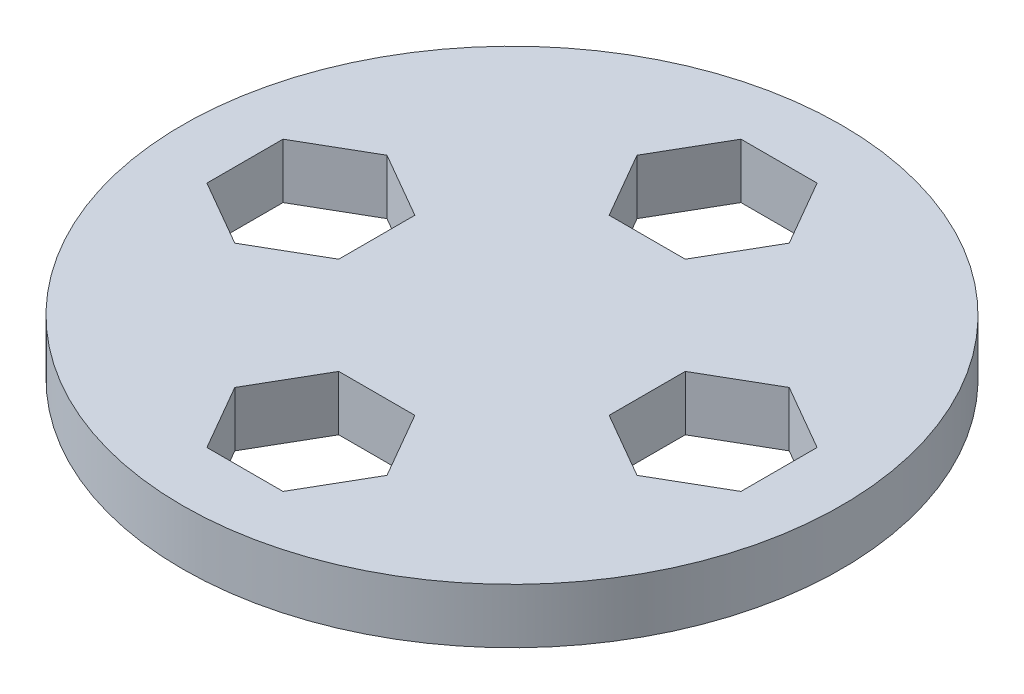
SolidWorks part; units mm, degrees
ref_plane "Alzado" through (0, 0, 0) normal (0, 0, 1) x (1, 0, 0)
ref_plane "Planta" through (0, 0, 0) normal (0, 1, 0) x (1, 0, 0)
ref_plane "Vista lateral" through (0, 0, 0) normal (1, 0, 0) x (0, 0, -1)
sketch "Croquis1" plane through (0, 0, 0) normal (0, 1, 0) x (1, 0, 0)
  circle A0 centre (0, 0) radius 8.5
  dimension "D1" = 17
extrude "Saliente-Extruir1" add sketch "Croquis1" along normal blind 2
sketch "Croquis2" plane through (0, 2, 0) normal (0, 1, 0) x (1, 0, 0)
  circle A0 centre (0, 0) radius 7.5
  dimension "D1" = 15
extrude "Saliente-Extruir2" add sketch "Croquis2" along normal blind 4
sketch "Croquis3" plane through (0, 6, 0) normal (0, 1, 0) x (1, 0, 0)
  circle A0 centre (0, 0) radius 15
  dimension "D1" = 30
extrude "Saliente-Extruir3" add sketch "Croquis3" along normal blind 2.5
fillet "Redondeo1" radius 3 1 edges at (0, 0, 8.5)
sketch "Croquis4" plane through (0, 8.5, 0) normal (0, 1, 0) x (1, 0, 0)
  line L0 (12.154, -1.7321) -> (12.154, 1.7321)
  line L1 (3.4641, 9.154) -> (1.7321, 12.154)
  line L2 (1.7321, 12.154) -> (-1.7321, 12.154)
  line L3 (-1.7321, 12.154) -> (-3.4641, 9.154)
  line L4 (-3.4641, 9.154) -> (-1.7321, 6.154)
  line L5 (-1.7321, 6.154) -> (1.7321, 6.154)
  line L6 (1.7321, 6.154) -> (3.4641, 9.154)
  line L7 (12.154, 1.7321) -> (9.154, 3.4641)
  line L8 (9.154, 3.4641) -> (6.154, 1.7321)
  line L9 (6.154, 1.7321) -> (6.154, -1.7321)
  line L10 (6.154, -1.7321) -> (9.154, -3.4641)
  line L11 (9.154, -3.4641) -> (12.154, -1.7321)
  line L12 (-1.7321, -12.154) -> (1.7321, -12.154)
  line L13 (1.7321, -12.154) -> (3.4641, -9.154)
  line L14 (3.4641, -9.154) -> (1.7321, -6.154)
  line L15 (1.7321, -6.154) -> (-1.7321, -6.154)
  line L16 (-1.7321, -6.154) -> (-3.4641, -9.154)
  line L17 (-3.4641, -9.154) -> (-1.7321, -12.154)
  line L18 (-12.154, 1.7321) -> (-12.154, -1.7321)
  line L19 (-12.154, -1.7321) -> (-9.154, -3.4641)
  line L20 (-9.154, -3.4641) -> (-6.154, -1.7321)
  line L21 (-6.154, -1.7321) -> (-6.154, 1.7321)
  line L22 (-6.154, 1.7321) -> (-9.154, 3.4641)
  line L23 (-9.154, 3.4641) -> (-12.154, 1.7321)
  circle A0 centre (0, 9.154) radius 3 construction
  point P29 (0, 0)
  dimension "D1" = 6
  dimension "D2" = 4
extrude "Cortar-Extruir1" cut sketch "Croquis4" against normal blind 2.5
sketch "Croquis5" plane through (0, 6, 0) normal (0, -1, 0) x (1, 0, 0)
  circle A0 centre (0, 0) radius 8.5
extrude "Cortar-Extruir2" cut sketch "Croquis5" along normal blind 10
